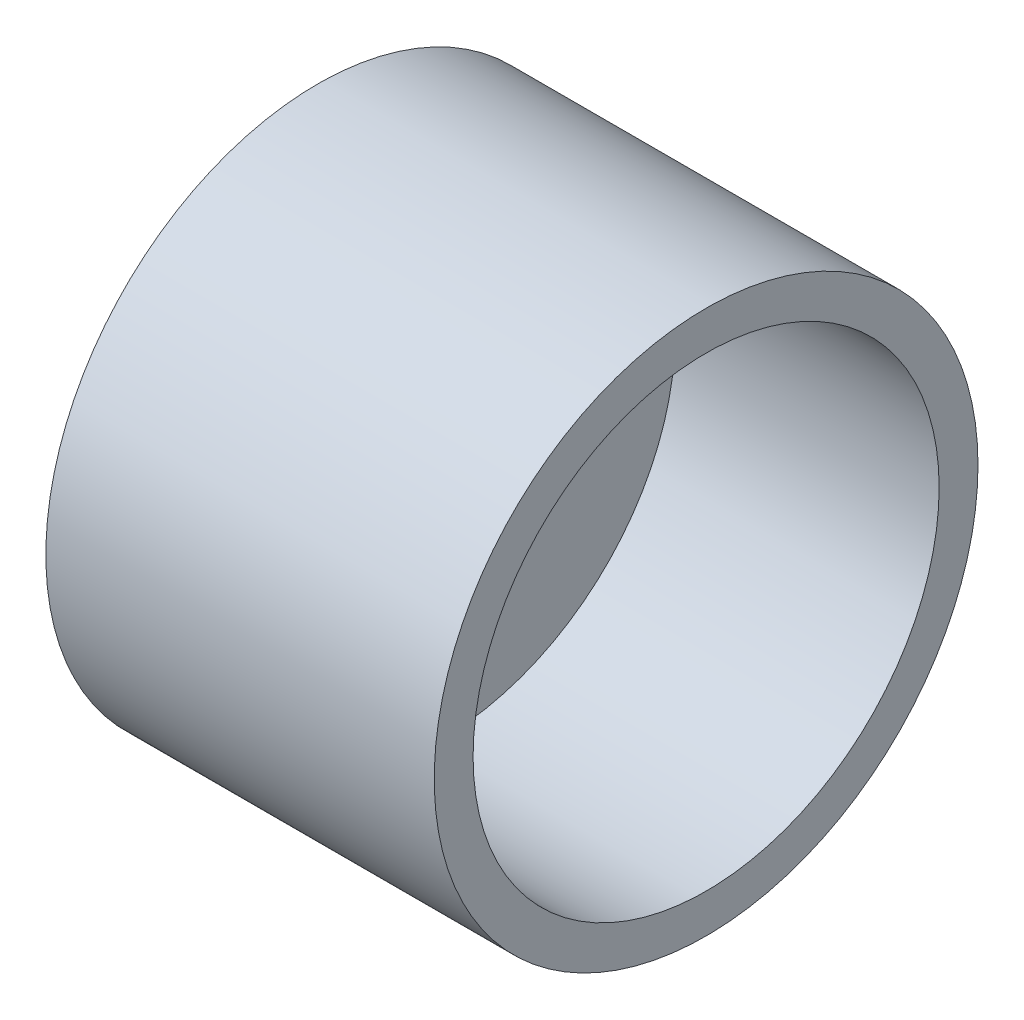
SolidWorks part; units mm, degrees
ref_plane "Front Plane" through (0, 0, 0) normal (0, 0, 1) x (1, 0, 0)
ref_plane "Top Plane" through (0, 0, 0) normal (0, 1, 0) x (1, 0, 0)
ref_plane "Right Plane" through (0, 0, 0) normal (1, 0, 0) x (0, 0, -1)
sketch "Sketch1" plane through (0, 0, 0) normal (1, 0, 0) x (0, 0, -1)
  circle A0 centre (0, 0) radius 17.5
  circle A1 centre (0, 0) radius 15
  circle A4 centre (0, 0) radius 1.5
  dimension "D1" = 35
  dimension "D2" = 3
  dimension "D3" = 30
extrude "Boss-Extrude1" add sketch "Sketch1" along normal blind 25 contours A0 A1 region at (0, 0, 17.005)
extrude "Boss-Extrude2" add sketch "Sketch1<3>" along normal blind 8 contours A1 region at (0, 0, 14.5757)
sketch "Sketch1<3>" plane through (0, 0, 0) normal (1, 0, 0) x (0, 0, -1) same geometry as "Sketch1"
